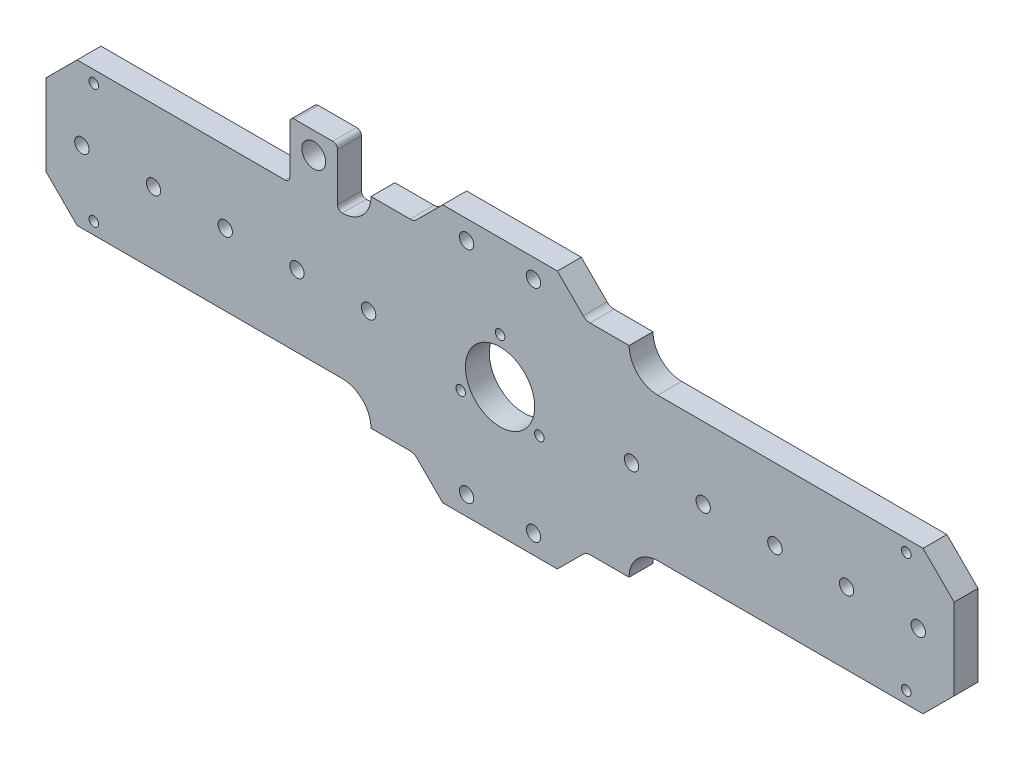
SolidWorks part; units mm, degrees
material "Thornel Mat VMA"
ref_plane "前视基准面" through (0, 0, 0) normal (0, 0, 1) x (1, 0, 0)
ref_plane "上视基准面" through (0, 0, 0) normal (0, 1, 0) x (1, 0, 0)
ref_plane "右视基准面" through (0, 0, 0) normal (1, 0, 0) x (0, 0, -1)
sketch "草图1" plane through (0, 0, 0) normal (0, 0, 1) x (1, 0, 0)
  line L1 (-95, -15) -> (95, -15) construction
  line L3 (-95, 15) -> (95, 15) construction
  line L4 (95, -15) -> (95, 15)
  line L5 (-95, -15) -> (95, 15) construction
  line L6 (-95, 15) -> (95, -15) construction
  line L7 (0, 0) -> (95, 0) construction
  line L8 (-12, 27) -> (12, 27)
  line L9 (12, 27) -> (18, 21)
  line L10 (18, 21) -> (33, 21) construction
  line L11 (33, 21) -> (33, 15) construction
  line L12 (33, 15) -> (95, 15)
  line L13 (0, 15) -> (0, -15) construction
  line L14 (33, -15) -> (95, -15)
  line L17 (12, -27) -> (18, -21)
  line L18 (-12, -27) -> (12, -27)
  line L19 (-12, -27) -> (-18, -21)
  line L22 (-33, -15) -> (-95, -15)
  line L23 (-95, -15) -> (-95, 15)
  line L24 (-33, 15) -> (-95, 15)
  line L27 (-12, 27) -> (-18, 21)
  line L28 (18, 21) -> (27, 21)
  line L29 (18, -21) -> (27, -21)
  line L30 (-18, -21) -> (-27, -21)
  line L31 (-18, 21) -> (-27, 21)
  circle A0 centre (0, 9.5) radius 1
  circle A2 centre (0, 0) radius 9.5 construction
  circle A6 centre (0, 0) radius 7.25
  arc A7 (27, 21) -> (33, 15) centre (33, 21) ccw
  arc A8 (27, -21) -> (33, -15) centre (33, -21) cw
  arc A9 (-27, 21) -> (-33, 15) centre (-33, 21) cw
  arc A10 (-27, -21) -> (-33, -15) centre (-33, -21) ccw
  circle A11 centre (8.2272, -4.75) radius 1
  circle A12 centre (-8.2272, -4.75) radius 1
  point P0 (0, 0)
  point P31 (0, -27)
  point P38 (0, 27)
  dimension "D1" = 2
  dimension "D2" = 19
  dimension "D7" = 14.5
  dimension "D3" = 3
  dimension "D4" = 30
  dimension "D5" = 190
  dimension "D8" = 12
  dimension "D9" = 135
  dimension "D10" = 6
  dimension "D11" = 15
  dimension "D12" = 12
extrude "凸台-拉伸1" add sketch "草图1" along normal blind 5
sketch "草图2" plane through (0, 0, 5) normal (0, 0, 1) x (1, 0, 0)
  line L0 (12, 27) -> (-12, 27) construction
  line L1 (-12, -27) -> (12, -27) construction
  circle A0 centre (7, 23) radius 1.5
  circle A1 centre (-7, 23) radius 1.5
  circle A2 centre (7, -23) radius 1.5
  circle A3 centre (-7, -23) radius 1.5
  dimension "D1" = 3
  dimension "D2" = 3
  dimension "D9" = 3
  dimension "D10" = 3
  dimension "D3" = 14
  dimension "D4" = 5
  dimension "D5" = 4
  dimension "D6" = 14
  dimension "D7" = 4
  dimension "D8" = 5
extrude "切除-拉伸1" cut sketch "草图2" against normal blind 10
sketch "草图3" plane through (0, 0, 5) normal (0, 0, 1) x (1, 0, 0)
  line L0 (95, -15) -> (95, 15) construction
  line L1 (87.5, 0) -> (72.5, 0) construction
  line L2 (0, -1000) -> (0, 49000) construction
  circle A0 centre (87.5, 0) radius 1.5
  circle A20 centre (72.5, 0) radius 1.5
  circle A21 centre (57.5, 0) radius 1.5
  circle A22 centre (-57.5, 0) radius 1.5
  circle A23 centre (-72.5, 0) radius 1.5
  circle A24 centre (-87.5, 0) radius 1.5
  circle A25 centre (42.5, 0) radius 1.5
  circle A26 centre (27.5, 0) radius 1.5
  circle A27 centre (-27.5, 0) radius 1.5
  circle A28 centre (-42.5, 0) radius 1.5
  dimension "D2" = 3
  dimension "D1" = 7.5
  dimension "D4" = 15
  dimension "D3" = 5
extrude "切除-拉伸2" cut sketch "草图3" against normal blind 10
fillet "圆角1" radius 2 4 edges at (-18, -21, 2.5) (18, -21, 2.5) (18, 21, 2.5) (-18, 21, 2.5)
chamfer "倒角1" distance 6.5 angle 45 4 edges at (-95, -15, 2.5) (-95, 15, 2.5) (95, -15, 2.5) (95, 15, 2.5)
sketch "草图4" plane through (0, 0, 5) normal (0, 0, 1) x (1, 0, 0)
  line L0 (95, 8.5) -> (88.5, 15) construction
  line L1 (88.5, 15) -> (33, 15) construction
  line L2 (33, -15) -> (88.5, -15) construction
  line L3 (95, 8.5) -> (88.5, 15) construction
  line L4 (0, -1000) -> (0, 49000) construction
  line L5 (95, -8.5) -> (95, 8.5) construction
  line L6 (95, 8.5) -> (88.5, 15) construction
  line L7 (91.75, 11.75) -> (89.9822, 9.9822) construction
  line L8 (-1078.1173, 0) -> (48921.8827, 0) construction
  circle A0 centre (85, 12.5) radius 1
  circle A2 centre (85, -12.5) radius 1
  circle A3 centre (89.9822, 9.9822) radius 1 construction
  circle A4 centre (89.9822, -9.9822) radius 1 construction
  circle A5 centre (-89.9822, -9.9822) radius 1 construction
  circle A6 centre (-85, -12.5) radius 1
  circle A7 centre (-89.9822, 9.9822) radius 1 construction
  circle A8 centre (-85, 12.5) radius 1
  dimension "D2" = 2
  dimension "D3" = 2
  dimension "D7" = 2
  dimension "D1" = 2.5
  dimension "D4" = 2.5
  dimension "D5" = 10
  dimension "D6" = 2.5
extrude "切除-拉伸3" cut sketch "草图4" against normal blind 10
sketch "草图5" plane through (0, 0, 5) normal (0, 0, 1) x (1, 0, 0)
  line L0 (0, 0) -> (-53.3, 0) construction
  line L1 (0, -1000) -> (0, 49000) construction
  line L2 (-53.3, 0) -> (-59.3, 0) construction
  line L3 (-53.3, 0) -> (-53.3, -20) construction
  line L4 (-53.3, -20) -> (-59.3, -20) construction
  line L5 (-59.3, 0) -> (-59.3, -20) construction
  circle A0 centre (-56.3, -15) radius 1.5
  circle A1 centre (-56.3, 5) radius 1.5
  circle A2 centre (56.3, 5) radius 1.5
  circle A3 centre (56.3, -15) radius 1.5
  dimension "D4" = 3
  dimension "D8" = 3
  dimension "D1" = 59.3
  dimension "D2" = 20
  dimension "D3" = 6
  dimension "D5" = 5
  dimension "D6" = 3
  dimension "D7" = 20
sketch "草图6" plane through (0, 0, 0) normal (0, 0, -1) x (-1, 0, 0)
  line L0 (34, 15) -> (34, 27)
  line L1 (33, 15) -> (88.5, 15) construction
  line L2 (34, 27) -> (44, 27)
  line L3 (44, 27) -> (44, 15)
  line L4 (95, 8.5) -> (95, -8.5) construction
  line L5 (38.9711, 22.5) -> (0, 0) construction
  line L6 (0, 0) -> (95, 0) construction
  line L7 (34, 15) -> (44, 15)
  circle A0 centre (0, 0) radius 45 construction
  circle A1 centre (38.9711, 22.5) radius 2.5
  dimension "D1" = 90
  dimension "D6" = 5
  dimension "D2" = 51
  dimension "D3" = 10
  dimension "D4" = 12
  dimension "D5" = 30
extrude "凸台-拉伸2" add sketch "草图6" against normal blind 5
fillet "圆角2" radius 1 4 edges at (-34, 27, 2.5) (-44, 27, 2.5) (-44, 15, 2.5) (-34, 15, 2.5)
